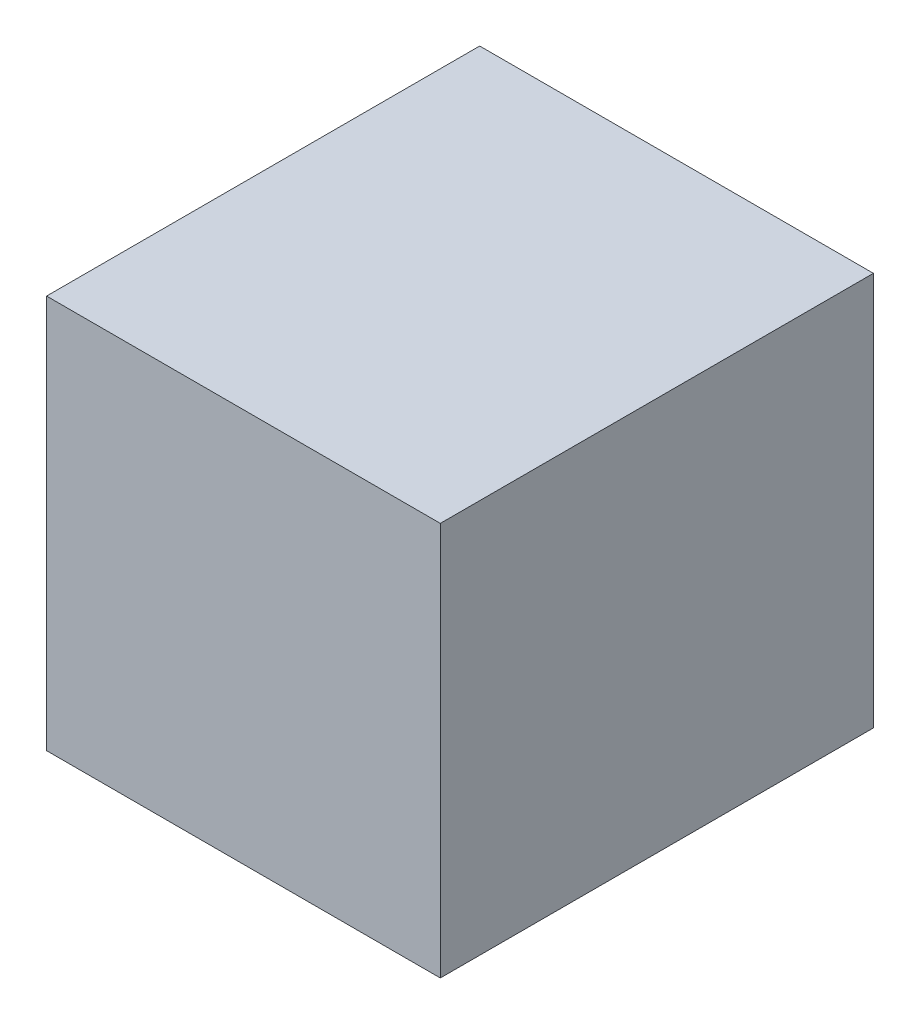
SolidWorks part; units mm, degrees
ref_plane "Front Plane" through (0, 0, 0) normal (0, 0, 1) x (1, 0, 0)
ref_plane "Top Plane" through (0, 0, 0) normal (0, 1, 0) x (1, 0, 0)
ref_plane "Right Plane" through (0, 0, 0) normal (1, 0, 0) x (0, 0, -1)
sketch "Sketch1" plane through (0, 0, 0) normal (0, 0, 1) x (1, 0, 0)
  line L1 (-50, -50) -> (50, -50)
  line L2 (-50, -50) -> (-50, 50)
  line L3 (-50, 50) -> (50, 50)
  line L4 (50, -50) -> (50, 50)
  line L5 (-50, -50) -> (50, 50) construction
  line L6 (-50, 50) -> (50, -50) construction
  point P0 (0, 0)
  dimension "D1" = 100
extrude "Boss-Extrude1" add sketch "Sketch1" along normal blind 110
ref_plane "Plane1" through (0, 0, 0) normal (-0.7071, 0.7071, 0) x (0.7071, 0.7071, 0)
ref_plane "Plane2" through (0, 0, 0) normal (-0.7071, -0.7071, 0) x (-0.7071, 0.7071, 0)
ref_axis "Axis1" through (0, 0, -5.5) along (0, 0, 1)
